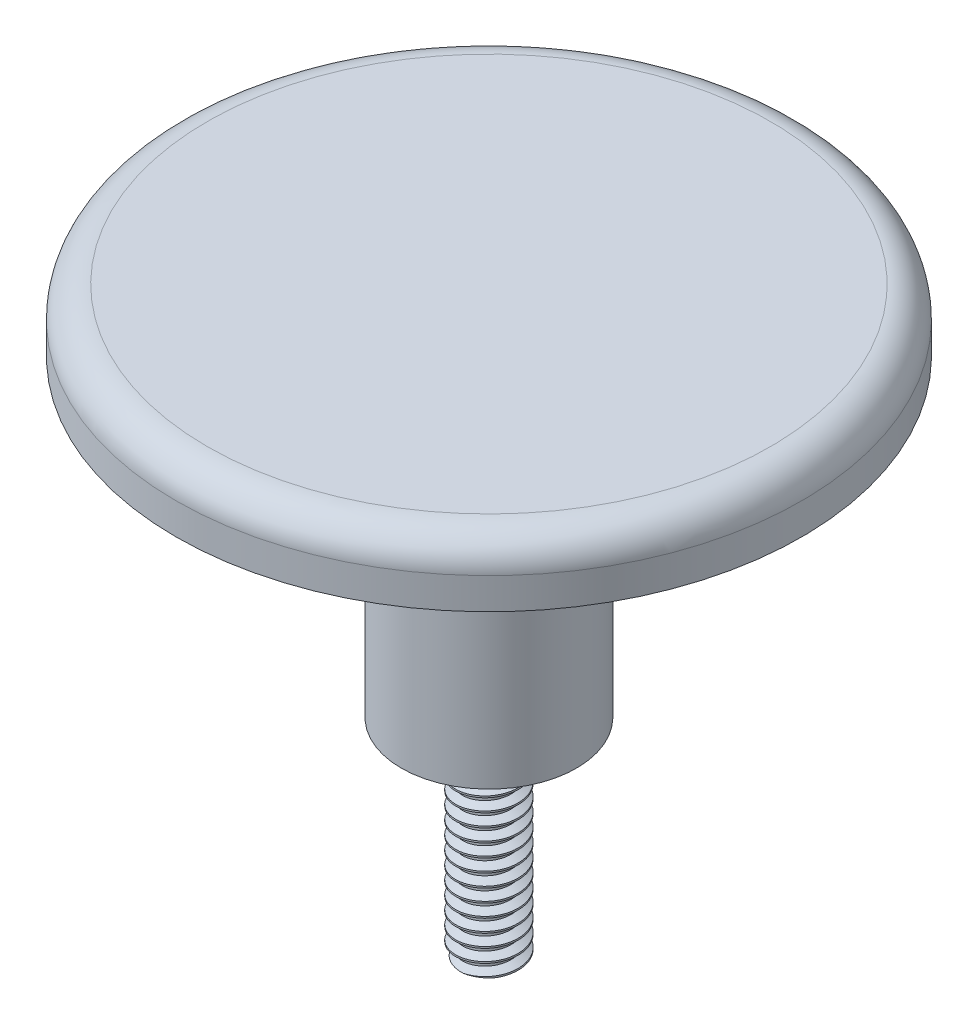
SolidWorks part; units mm, degrees
material "PE High Density"
ref_plane "Front Plane" through (0, 0, 0) normal (0, 0, 1) x (1, 0, 0)
ref_plane "Top Plane" through (0, 0, 0) normal (0, 1, 0) x (1, 0, 0)
ref_plane "Right Plane" through (0, 0, 0) normal (1, 0, 0) x (0, 0, -1)
sketch "Sketch1" plane through (0, 0, 0) normal (0, 1, 0) x (1, 0, 0)
  circle A0 centre (0, 0) radius 2.54
extrude "Boss-Extrude1" add sketch "Sketch1" along normal blind 16.51
sketch "Sketch4" plane through (0, 16.51, 0) normal (0, 1, 0) x (1, 0, 0)
  circle A0 centre (0, 0) radius 7.112
extrude "Boss-Extrude2" add sketch "Sketch4" along normal blind 25.4
thread "Thread2" pitch 1.0583 method cut profile "Thread Profile2" start angle 0, offset 0, length 16.51, pitch 1.0583, diameter 5.08
ref_plane "Plane2" through (-2.54, 16.51, 0) normal (0, 0, 1) x (-1, 0, 0)
sketch "Thread Profile2" plane through (-2.54, 16.51, 0) normal (0, 0, 1) x (-1, 0, 0)
  line L0 (0, 0) -> (0, 1.0583) construction
  line L11 (0, 0) -> (0, 0.926)
  line L12 (0, 0.926) -> (-0.5728, 0.5953)
  line L13 (-0.5728, 0.5953) -> (-0.5728, 0.3307)
  line L15 (-0.5728, 0.3307) -> (0, 0)
  line L17 (-0.5728, 0.463) -> (0, 0.463) construction
  point P2 (0, 0)
  dimension "Pitch" = 1.0583
  dimension "Profile_Angle" = 60
  dimension "Profile_Land" = 0.2646
  dimension "Profile_Height" = 0.5728
sketch "Sketch7" plane through (0, 41.91, 0) normal (0, 1, 0) x (1, 0, 0)
  circle A0 centre (0, 0) radius 25.4
extrude "Boss-Extrude3" add sketch "Sketch7" along normal blind 5.08 contours A0
fillet "Fillet1" radius 2.54 1 edges at (0, 46.99, 25.4)
